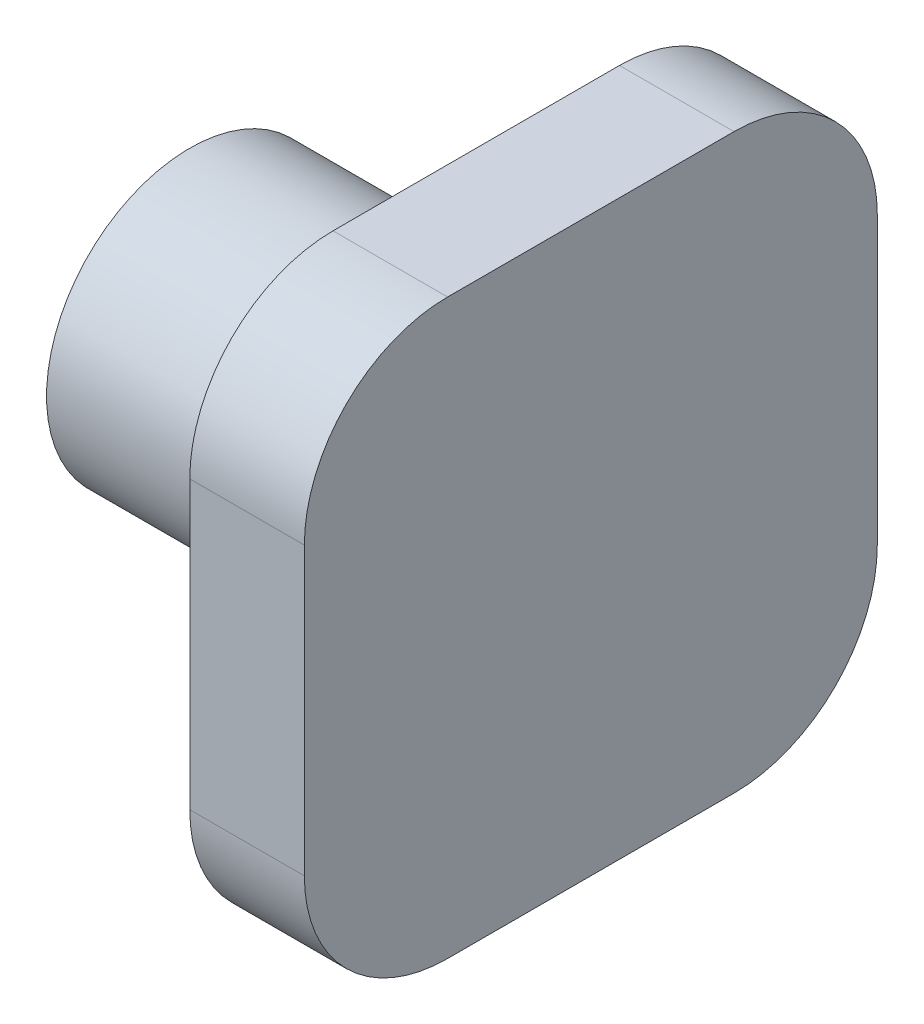
SolidWorks part; units mm, degrees
material "PET"
ref_plane "Front Plane" through (0, 0, 0) normal (0, 0, 1) x (1, 0, 0)
ref_plane "Top Plane" through (0, 0, 0) normal (0, 1, 0) x (1, 0, 0)
ref_plane "Right Plane" through (0, 0, 0) normal (1, 0, 0) x (0, 0, -1)
sketch "Sketch1" plane through (0, 0, 0) normal (1, 0, 0) x (0, 0, -1)
  circle A0 centre (0, 0) radius 4.445
  circle A1 centre (0, 0) radius 6.35
  dimension "D1" = 8.89
  dimension "D2" = 12.7
extrude "Boss-Extrude1" add sketch "Sketch1" along normal blind 12.7
thread "Thread1" start angle 0, offset 0, length 0, pitch 2.54, diameter 8.89
ref_plane "Plane1" through (0, 0, -4.445) normal (0, -1, 0) x (0, 0, -1)
sketch "Thread Profile1" plane through (0, 0, -4.445) normal (0, -1, 0) x (0, 0, -1)
  line L0 (0, 0) -> (0, 2.54) construction
  line L11 (0, 0) -> (0, 2.2225)
  line L12 (0, 2.2225) -> (-1.3748, 1.4287)
  line L13 (-1.3748, 1.4287) -> (-1.3748, 0.7937)
  line L15 (-1.3748, 0.7937) -> (0, 0)
  line L17 (-1.3748, 1.1112) -> (0, 1.1112) construction
  point P2 (0, 0)
  dimension "Pitch" = 2.54
  dimension "Profile_Angle" = 60
  dimension "Profile_Land" = 0.635
  dimension "Profile_Height" = 1.3748
sketch "Sketch4" plane through (12.7, 0, 0) normal (1, 0, 0) x (0, 0, -1)
  line L1 (-6.35, 12.7) -> (6.35, 12.7)
  line L2 (-12.7, 6.35) -> (-12.7, -6.35)
  line L3 (-6.35, -12.7) -> (6.35, -12.7)
  line L4 (12.7, 6.35) -> (12.7, -6.35)
  arc A0 (6.35, -12.7) -> (12.7, -6.35) centre (6.35, -6.35) ccw
  arc A1 (-12.7, -6.35) -> (-6.35, -12.7) centre (-6.35, -6.35) ccw
  arc A2 (-6.35, 12.7) -> (-12.7, 6.35) centre (-6.35, 6.35) ccw
  arc A3 (6.35, 12.7) -> (12.7, 6.35) centre (6.35, 6.35) cw
  point P7 (12.7, -12.7)
  point P12 (-12.7, 12.7)
  point P15 (12.7, 12.7)
  dimension "D5" = 6.35
  dimension "D1" = 25.4
  dimension "D2" = 25.4
  dimension "D3" = 12.7
  dimension "D4" = 12.7
extrude "Boss-Extrude2" add sketch "Sketch4" along normal blind 5.08
